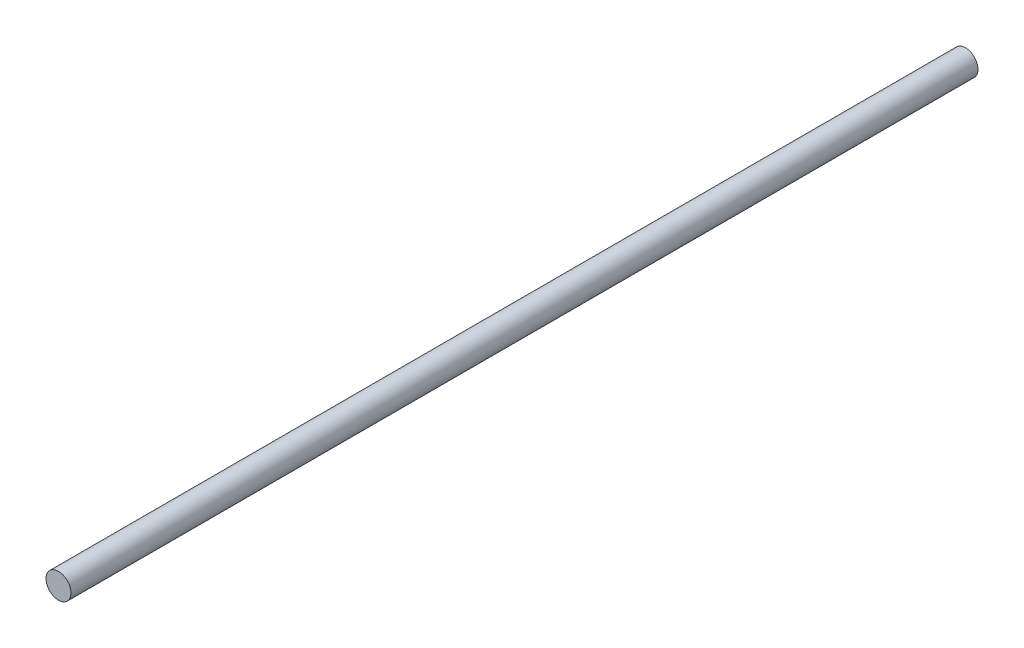
SolidWorks part; units mm, degrees
material "1023 Arkusz stali węglowej (SS)"
ref_plane "Płaszczyzna przednia" through (0, 0, 0) normal (0, 0, 1) x (1, 0, 0)
ref_plane "Płaszczyzna górna" through (0, 0, 0) normal (0, 1, 0) x (1, 0, 0)
ref_plane "Płaszczyzna prawa" through (0, 0, 0) normal (1, 0, 0) x (0, 0, -1)
sketch "Szkic1" plane through (0, 0, 0) normal (0, 0, 1) x (1, 0, 0)
  circle A0 centre (0, 0) radius 4
  dimension "D1" = 8
extrude "Dodanie-wyciągnięcie1" add sketch "Szkic1" along normal blind 290.06
